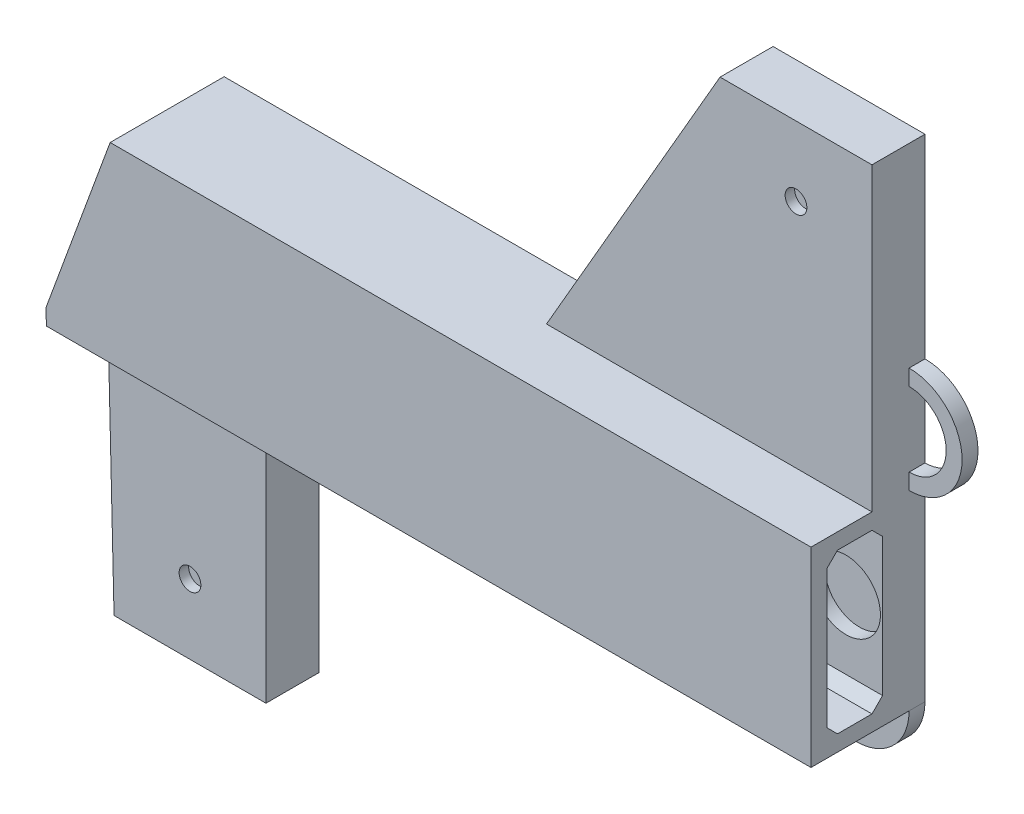
SolidWorks part; units mm, degrees
note: The reader was unsure of these and kept them because the rebuilt part matched: shared geometry of "Sketch3<4>", "Sketch3<8>", "Sketch3<9>".
ref_plane "Front Plane" through (0, 0, 0) normal (0, 0, 1) x (1, 0, 0)
ref_plane "Top Plane" through (0, 0, 0) normal (0, 1, 0) x (1, 0, 0)
ref_plane "Right Plane" through (0, 0, 0) normal (1, 0, 0) x (0, 0, -1)
sketch "Sketch1" plane through (0, 0, 0) normal (0, 0, 1) x (1, 0, 0)
  line L0 (-315, 0) -> (315, 0)
  line L1 (-285.1688, 41.9) -> (-262.5188, 41.9)
  line L2 (-285.1688, 41.9) -> (-285.1688, 21.6)
  line L3 (-285.1688, 21.6) -> (-262.5188, 21.6)
  line L4 (-262.5188, 41.9) -> (-262.5188, 21.6)
  line L5 (262.5187, 41.9) -> (285.1687, 41.9)
  line L6 (262.5187, 41.9) -> (262.5187, 21.6)
  line L7 (262.5187, 21.6) -> (285.1687, 21.6)
  line L8 (285.1687, 41.9) -> (285.1687, 21.6)
  line L9 (-170.8687, 160.7) -> (-148.2188, 160.7)
  line L10 (-170.8687, 160.7) -> (-170.8687, 140.4)
  line L11 (-170.8687, 140.4) -> (-148.2188, 140.4)
  line L12 (-148.2188, 160.7) -> (-148.2188, 140.4)
  line L13 (148.2188, 160.7) -> (170.8688, 160.7)
  line L14 (148.2188, 160.7) -> (148.2188, 140.4)
  line L15 (148.2188, 140.4) -> (170.8688, 140.4)
  line L16 (170.8688, 160.7) -> (170.8688, 140.4)
  line L17 (-273.8438, 31.75) -> (273.8438, 31.75)
  line L18 (-159.5437, 150.55) -> (159.5437, 150.55)
  line L19 (315, 0) -> (315, 30.6)
  line L20 (-248.5188, 79.7) -> (-214.0187, 79.7)
  line L21 (-248.5188, 79.7) -> (-248.5188, 44.9)
  line L22 (-248.5188, 44.9) -> (-214.0187, 44.9)
  line L23 (-214.0187, 79.7) -> (-214.0187, 44.9)
  line L24 (-189.0187, 88.6) -> (-129.3687, 88.6)
  line L25 (-189.0187, 88.6) -> (-189.0187, 48.9)
  line L26 (-189.0187, 48.9) -> (-129.3687, 48.9)
  line L27 (-129.3687, 88.6) -> (-129.3687, 48.9)
  line L28 (-8.5687, 81.6) -> (61.1313, 81.6)
  line L29 (-8.5687, 81.6) -> (-8.5687, 46.9)
  line L30 (-8.5687, 46.9) -> (61.1313, 46.9)
  line L31 (61.1313, 81.6) -> (61.1313, 46.9)
  line L32 (315, 30.6) -> (254, 197)
  line L33 (254, 197) -> (-254, 197)
  line L34 (-254, 197) -> (-315, 30.6)
  line L35 (-315, 30.6) -> (-315, 0)
  line L36 (-315, 4.4515) -> (-244.4143, 197)
  circle A0 centre (-273.8438, 31.75) radius 2.05
  circle A1 centre (273.8438, 31.75) radius 2.05
  circle A2 centre (-159.5437, 150.55) radius 2.05
  circle A3 centre (159.5437, 150.55) radius 2.05
  circle A4 centre (-195.5187, 59.9) radius 2.05
  point P6 (0, 0)
  point P7 (-273.8438, 41.9)
  point P9 (-262.5187, 31.75)
  point P18 (273.8438, 41.9)
  point P19 (285.1688, 31.75)
  point P26 (-159.5437, 160.7)
  point P27 (-148.2188, 150.55)
  point P34 (159.5437, 160.7)
  point P35 (170.8687, 150.55)
  point P36 (0, 31.75)
  point P37 (0, 150.55)
  point P57 (0, 197)
  dimension "D3" = 4.1
  dimension "D7" = 4.1
  dimension "D10" = 4.1
  dimension "D13" = 4.1
  dimension "D18" = 4.1
  dimension "D1" = 22.65
  dimension "D2" = 20.3
  dimension "D4" = 630
  dimension "D5" = 22.65
  dimension "D6" = 20.3
  dimension "D8" = 22.65
  dimension "D9" = 20.3
  dimension "D11" = 22.65
  dimension "D12" = 20.3
  dimension "D14" = 547.6875
  dimension "D15" = 31.75
  dimension "D16" = 98.5
  dimension "D17" = 319.0875
  dimension "D19" = 6.5
  dimension "D20" = 69.7
  dimension "D21" = 34.7
  dimension "D22" = 59.65
  dimension "D23" = 39.7
  dimension "D24" = 34.5
  dimension "D25" = 34.8
  dimension "D26" = 14
  dimension "D27" = 3
  dimension "D28" = 25
  dimension "D29" = 4
  dimension "D30" = 11
  dimension "D31" = 120.8
  dimension "D32" = 2
  dimension "D33" = 30.6
  dimension "D34" = 508
  dimension "D35" = 36.3
  dimension "D36" = 197
  dimension "D37" = 9
sketch "Sketch2" plane through (0, 0, 0) normal (0, 0, 1) x (1, 0, 0)
  line L0 (-315, 0) -> (315, 0) construction
  line L1 (-375, 104) -> (375, 104)
  line L2 (-375, 104) -> (-375, 74)
  line L3 (-375, 74) -> (375, 74)
  line L4 (375, 104) -> (375, 74)
  line L6 (-315, 30.6) -> (-315, 0) construction
  line L7 (315, 0) -> (315, 30.6) construction
  dimension "D1" = 74
  dimension "D2" = 30
  dimension "D3" = 60
  dimension "D4" = 60
sketch "Sketch5" plane through (-8.3611, 207.407, 0) normal (0, 0, 1) x (0.7071, 0.7071, 0)
  line L1 (-608.5386, 190.157) -> (-388.5386, 190.157)
  line L2 (-608.5386, 190.157) -> (-608.5386, -29.843)
  line L3 (-608.5386, -29.843) -> (-388.5386, -29.843)
  line L4 (-388.5386, 190.157) -> (-388.5386, -29.843)
  dimension "D1" = 220
  dimension "D2" = 220
sketch "Sketch3" plane through (0, 0, 0) normal (0, 0, 1) x (1, 0, 0)
  line L0 (-148.2188, 160.7) -> (-148.2188, 140.4) construction
  line L1 (-288.1688, 18.6) -> (-145.2188, 18.6)
  line L2 (-288.1688, 18.6) -> (-288.1688, 163.7)
  line L3 (-288.1688, 163.7) -> (-145.2188, 163.7)
  line L4 (-145.2188, 18.6) -> (-145.2188, 163.7)
  line L5 (-170.8687, 160.7) -> (-148.2188, 160.7) construction
  line L6 (-285.1688, 21.6) -> (-262.5188, 21.6) construction
  line L7 (-285.1688, 41.9) -> (-285.1688, 21.6) construction
  line L8 (-288.1688, 18.6) -> (-289.5045, 74)
  line L9 (-315, 4.4515) -> (-244.4143, 197) construction
  line L10 (-375, 74) -> (375, 74) construction
  line L11 (-289.5045, 74) -> (-256.6217, 163.7)
  line L12 (-173.8687, 163.7) -> (-206.6045, 107)
  line L13 (-285.1688, 21.6) -> (-262.5188, 21.6)
  line L14 (-285.1688, 21.6) -> (-285.1688, 41.9)
  line L15 (-285.1688, 41.9) -> (-262.5188, 41.9)
  line L16 (-262.5188, 21.6) -> (-262.5188, 41.9)
  line L17 (-148.2188, 160.7) -> (-170.8687, 160.7)
  line L18 (-148.2188, 160.7) -> (-148.2188, 140.4)
  line L19 (-148.2188, 140.4) -> (-170.8687, 140.4)
  line L20 (-170.8687, 160.7) -> (-170.8687, 140.4)
  line L21 (-206.6045, 107) -> (-277.4071, 107)
  line L22 (-375, 104) -> (375, 104) construction
  line L23 (-259.5188, 18.6) -> (-259.5188, 71)
  line L24 (-259.5188, 71) -> (-145.2188, 71)
  line L25 (-259.5188, 71) -> (-289.4321, 71)
  line L26 (-206.6045, 107) -> (-145.2188, 107)
  circle A0 centre (-159.5437, 150.55) radius 2.05
  circle A1 centre (-273.8438, 31.75) radius 2.05
  dimension "D1" = 3
  dimension "D2" = 3
  dimension "D3" = 3
  dimension "D4" = 3
  dimension "D5" = 3
  dimension "D6" = 120
  dimension "D7" = 3
  dimension "D8" = 3
  dimension "D9" = 3
extrude "Boss-Extrude1" add sketch "Sketch3" against normal blind 8 contours L23 L24 L4 L3 L12 L21 L11 L2 L1 L20 L17 L18 L19 L16 L13 L14 L15 | L25 L2 L11 L8 | L2 L25 L8 | L23 L25 L2 L1 L16 L13 L14 L15 | L12 L26 L4 L3 L20 L17 L18 L19
extrude "Boss-Extrude2" add sketch "Sketch3<4>" along normal blind 2 separate body contours L17 L20 L19 L18 A0 | L13 L16 L15 L14 A1 | L23 L25 L2 L1 L16 L13 L14 L15 | L2 L25 L8 | L25 L2 L11 L8 | L25 L24 L4 L3 L12 L21 L11 L2 L20 L17 L18 L19 | L26 L21 L11 L2 L25 L24 L4
sketch "Sketch3<4>" plane through (0, 0, 0) normal (0, 0, 1) x (1, 0, 0) same geometry as "Sketch3"
extrude "Boss-Extrude3" add sketch "Sketch3<8>" along normal blind 13.5 contours L26 L21 L11 L2 L25 L24 L4 | L25 L2 L11 L8
sketch "Sketch3<8>" plane through (0, 0, 0) normal (0, 0, 1) x (1, 0, 0) same geometry as "Sketch3"
sketch "Sketch4" plane through (-145.2188, 0, 0) normal (1, 0, 0) x (0, 0, -1)
  line L0 (-13.5, 71) -> (-13.5, 107) construction
  line L1 (-10.5, 74) -> (0, 74)
  line L2 (-10.5, 74) -> (-10.5, 104)
  line L3 (-10.5, 104) -> (0, 104)
  line L4 (0, 74) -> (0, 104)
  line L5 (0, 4.4515) -> (0, 197) construction
  line L6 (8, 71) -> (-13.5, 71) construction
  line L7 (-13.5, 107) -> (-2, 107) construction
  dimension "D1" = 3
  dimension "D2" = 0
  dimension "D3" = 3
  dimension "D4" = 3
  dimension "D5" = 10.5
  dimension "D6" = 30
extrude "Cut-Extrude1" cut sketch "Sketch4" against normal through all
sketch "Sketch6" plane through (0, 0, 0) normal (0, 0, 1) x (1, 0, 0)
  line L1 (-375, 104) -> (-145.2188, 104)
  line L2 (-375, 104) -> (-375, 74)
  line L3 (-375, 74) -> (-145.2188, 74)
  line L4 (-145.2188, 104) -> (-145.2188, 74)
  dimension "D1" = 229.7812
  dimension "D2" = 30
chamfer "Chamfer1" distance 2 angle 45 4 edges at (-217.3616, 74, 10.5) (-217.3616, 74, 0) (-211.8628, 104, 0) (-211.8628, 104, 10.5)
sketch "Sketch7" plane through (0, 0, 0) normal (0, 0, 1) x (1, 0, 0)
  line L0 (-145.2188, 71) -> (-145.2188, 107) construction
  line L1 (-145.2188, 76) -> (-145.2188, 102) construction
  circle A0 centre (-234.2188, 89) radius 6.5
  circle A1 centre (-152.1188, 89) radius 6.5
  point P4 (-145.2188, 89)
  point P11 (-145.6188, 89)
  dimension "D2" = 13
  dimension "D1" = 89
  dimension "D3" = 0.4
extrude "Cut-Extrude3" cut sketch "Sketch7" against normal blind 2.5 contours A1
sketch "Sketch8" plane through (0, 0, -8) normal (0, 0, -1) x (-1, 0, 0)
  circle A0 centre (234.2188, 89) radius 6.5
extrude "Cut-Extrude4" cut sketch "Sketch8" against normal offset from surface (7 mm away) 1 up to face at (-145.6188, 89, 0)
sketch "Sketch9" plane through (0, 0, -8) normal (0, 0, -1) x (-1, 0, 0)
  line L0 (145.2188, 71) -> (289.4321, 71) construction
  line L1 (145.2188, 71) -> (145.2188, 107) construction
  line L2 (165.2188, 71) -> (162.2188, 71)
  line L3 (148.2188, 71) -> (145.2188, 71)
  line L4 (145.2188, 107) -> (145.2188, 163.7) construction
  line L5 (145.2188, 127) -> (145.2188, 124)
  line L6 (145.2188, 110) -> (145.2188, 107)
  circle A0 centre (155.2188, 71) radius 10
  circle A1 centre (155.2188, 71) radius 7
  circle A2 centre (145.2188, 117) radius 10
  circle A3 centre (145.2188, 117) radius 7
  line M7 (145.2188, 163.7) -> (145.2188, 71)
  line M8 (145.2188, 71) -> (259.5188, 71)
  dimension "D1" = 20
  dimension "D2" = 3
extrude "Boss-Extrude4" add sketch "Sketch9" against normal blind 3 separate body contours A1 A0 M8 | A3 A2 M7
extrude "Boss-Extrude5" add sketch "Sketch3<9>" along normal blind 0.2 contours A0 | A1
sketch "Sketch3<9>" plane through (0, 0, 0) normal (0, 0, 1) x (1, 0, 0) same geometry as "Sketch3"
